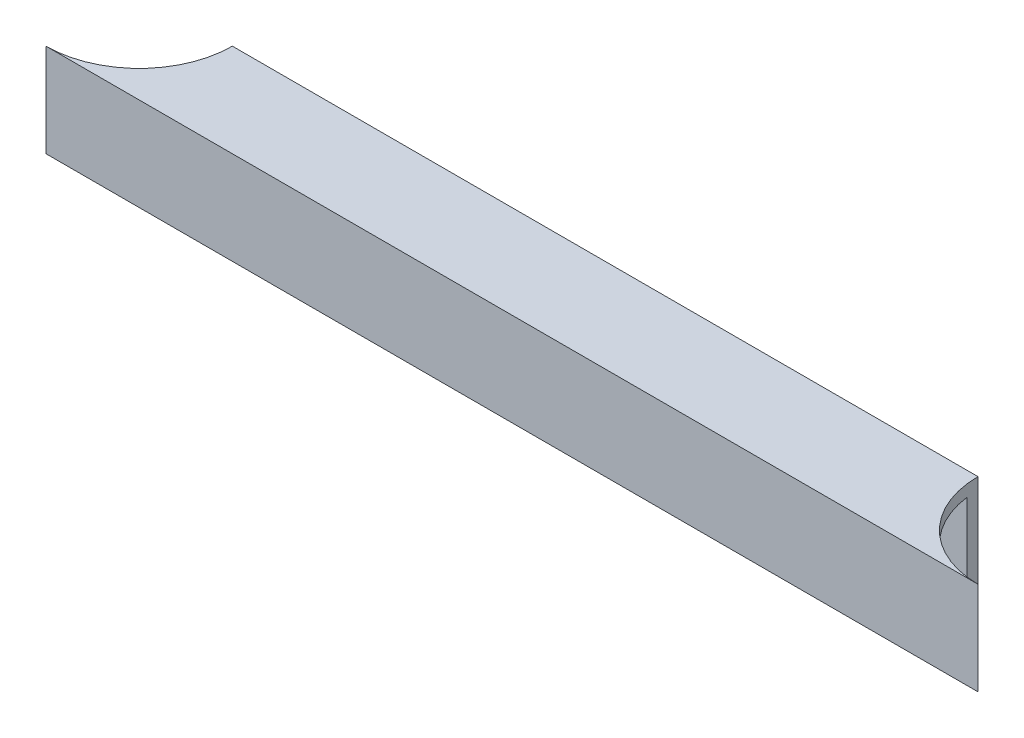
SolidWorks part; units mm, degrees
material "6061 Alloy"
ref_plane "Front Plane" through (0, 0, 0) normal (0, 0, 1) x (1, 0, 0)
ref_plane "Top Plane" through (0, 0, 0) normal (0, 1, 0) x (1, 0, 0)
ref_plane "Right Plane" through (0, 0, 0) normal (1, 0, 0) x (0, 0, -1)
sketch "Sketch1" plane through (0, 0, 0) normal (0, 1, 0) x (1, 0, 0)
  line L0 (-85.497, 49.3617) -> (-93.7459, 54.1242) construction
  line L1 (0, 146.647) -> (-127, -73.3235) construction
  line L2 (-127, -73.3235) -> (127, -73.3235) construction
  line L3 (127, -73.3235) -> (0, 146.647) construction
  line L4 (0, 197.447) -> (-170.9941, -98.7235) construction
  line L5 (-170.9941, -98.7235) -> (170.9941, -98.7235) construction
  line L6 (170.9941, -98.7235) -> (0, 197.447) construction
  line L7 (0, -98.7235) -> (0, -108.2485) construction
  line L8 (-127, -98.7235) -> (127, -98.7235)
  line L9 (0, 216.497) -> (-187.4919, -108.2485) construction
  line L10 (-187.4919, -108.2485) -> (187.4919, -108.2485) construction
  line L11 (187.4919, -108.2485) -> (0, 216.497) construction
  line L12 (101.6, -73.3235) -> (-101.6, -73.3235)
  circle A0 centre (0, 0) radius 73.3235 construction
  circle A1 centre (127, -73.3235) radius 25.4 construction
  circle A2 centre (-127, -73.3235) radius 25.4 construction
  circle A3 centre (0, 0) radius 98.7235 construction
  circle A4 centre (0, 0) radius 108.2485 construction
  arc A5 (-127, -98.7235) -> (-101.6, -73.3235) centre (-127, -73.3235) ccw
  arc A6 (127, -98.7235) -> (101.6, -73.3235) centre (127, -73.3235) cw
  dimension "D1" = 304.8
  dimension "D2" = 50.8
  dimension "D3" = 9.525
  dimension "D4" = 374.9837
  dimension "D5" = 25.4
extrude "Boss-Extrude1" add sketch "Sketch1" along normal blind 25.4 contours L8 A6 L12 A5 region at (0, 0, 86.3813)
sketch "Sketch2" plane through (0, 0, 0) normal (1, 0, 0) x (0, 0, -1)
  line L0 (-95.5485, 22.225) -> (-76.4985, 22.225)
  line L1 (-98.7235, 25.4) -> (-73.3235, 25.4) construction
  line L2 (-98.7235, 25.4) -> (-98.7235, 0) construction
  line L3 (-98.7235, 0) -> (-73.3235, 0) construction
  line L4 (-73.3235, 25.4) -> (-73.3235, 0) construction
  line L5 (-76.4985, 22.225) -> (-76.4985, 3.175)
  line L6 (-95.5485, 3.175) -> (-76.4985, 3.175)
  line L7 (-95.5485, 22.225) -> (-95.5485, 3.175)
  dimension "D1" = 3.175
extrude "Cut-Extrude1" cut sketch "Sketch2" against normal through all both and the other way through all
